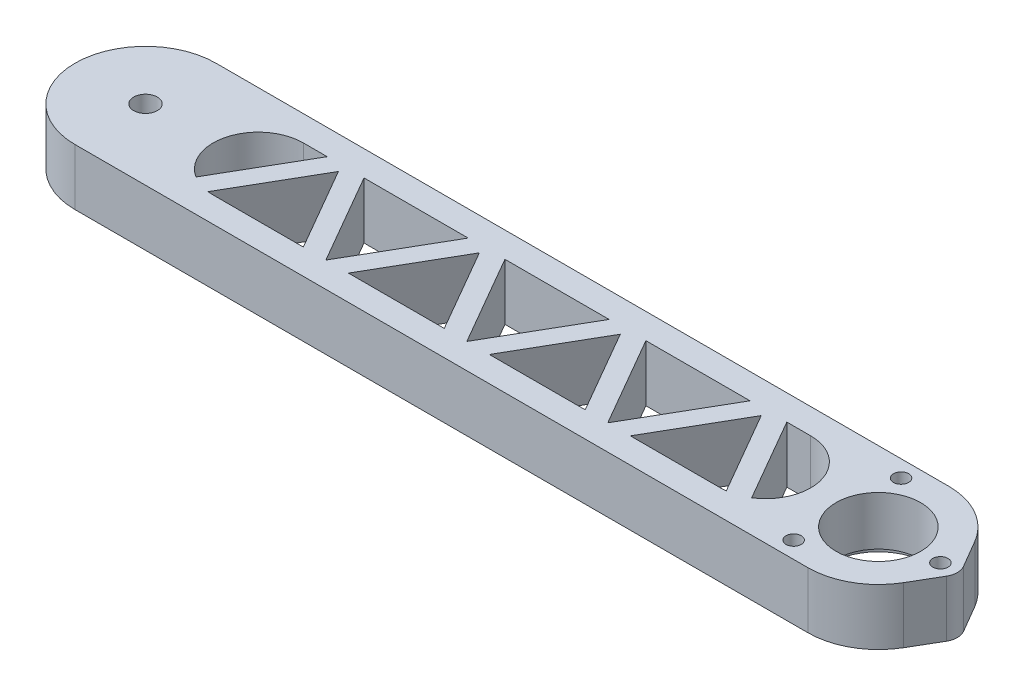
SolidWorks part; units mm, degrees
ref_plane "前视基准面" through (0, 0, 0) normal (0, 0, 1) x (1, 0, 0)
ref_plane "上视基准面" through (0, 0, 0) normal (0, 1, 0) x (1, 0, 0)
ref_plane "右视基准面" through (0, 0, 0) normal (1, 0, 0) x (0, 0, -1)
sketch "草图1" plane through (0, 0, 0) normal (0, 1, 0) x (1, 0, 0)
  line L0 (-65, 0) -> (65, 0) construction
  line L1 (-65, 12.5) -> (65, 12.5)
  line L2 (-65, -12.5) -> (65, -12.5)
  arc A0 (-65, 12.5) -> (-65, -12.5) centre (-65, 0) ccw
  arc A1 (65, -12.5) -> (65, 12.5) centre (65, 0) ccw
  point P2 (0, 0)
  dimension "D2" = 12.5
  dimension "D1" = 130
extrude "凸台-拉伸1" add sketch "草图1" along normal blind 10
sketch "草图10" plane through (0, 0, 0) normal (0, -1, 0) x (1, 0, 0)
  line L0 (75.7955, -6.3014) -> (78.5909, -1.5123)
  line L3 (75.7955, 6.3014) -> (78.5909, 1.5123)
  line L4 (75.7955, -6.3014) -> (75.7955, 6.3014)
  line L5 (76, 0) -> (77.5, 0) construction
  circle A5 centre (76, 0) radius 3 construction
  arc A6 (65, -12.5) -> (65, 12.5) centre (65, 0) ccw construction
  arc A7 (78.5909, -1.5123) -> (78.5909, 1.5123) centre (76, 0) ccw
  dimension "D1" = 6
  dimension "D2" = 1.5
extrude "凸台-拉伸5" add sketch "草图10" against normal up to surface (10 mm away) up to face at (0, 10, 0)
sketch "草图7" plane through (0, 10, 0) normal (0, 1, 0) x (1, 0, 0)
  circle A0 centre (65, 0) radius 7.5
  dimension "D1" = 15
extrude "切除-拉伸2" cut sketch "草图7" against normal up to next
sketch "草图8" plane through (0, 0, 0) normal (0, 1, 0) x (1, 0, 0)
  circle A0 centre (65, 0) radius 8.75
  dimension "D1" = 17.5
extrude "切除-拉伸3" cut sketch "草图8" along normal blind 1.3
sketch "草图9" plane through (0, 0, 0) normal (0, -1, 0) x (1, 0, 0)
  line L0 (65, 0) -> (54, 0) construction
  line L1 (65, 0) -> (59.5, 9.5263) construction
  circle A0 centre (65, 0) radius 11 construction
  circle A5 centre (59.5, 9.5263) radius 1.35
  circle A9 centre (76, 0) radius 1.35
  circle A10 centre (59.5, -9.5263) radius 1.35
  point P12 (65, 0)
  point P15 (65, 0)
  dimension "22" = 22
  dimension "D3" = 2.7
  dimension "D2" = 60
  dimension "D1" = 3
extrude "切除-拉伸4" cut sketch "草图9" against normal up to next
sketch "草图12" plane through (0, 10, 0) normal (0, 1, 0) x (1, 0, 0)
  circle A0 centre (-65, 0) radius 2.1
  dimension "D1" = 4.2
extrude "切除-拉伸5" cut sketch "草图12" against normal up to next
sketch "草图13" plane through (0, 10, 0) normal (0, 1, 0) x (1, 0, 0)
  line L0 (-45, 0) -> (45, 0) construction
  line L1 (-45, 8) -> (45, 8)
  line L2 (-45, -8) -> (45, -8)
  arc A0 (-45, 8) -> (-45, -8) centre (-45, 0) ccw
  arc A1 (45, -8) -> (45, 8) centre (45, 0) ccw
  point P2 (0, 0)
  dimension "D1" = 8
  dimension "D2" = 90
extrude "切除-拉伸6" cut sketch "草图13" against normal up to next
sketch "草图14" plane through (0, 10, 0) normal (0, 1, 0) x (1, 0, 0)
  line L5 (-45, -8) -> (45, -8) construction
  line L6 (45, 8) -> (-45, 8) construction
  line L7 (0, -8) -> (9.2376, 8)
  line L8 (9.2376, 8) -> (13.2376, 8)
  line L9 (13.2376, 8) -> (4, -8)
  line L10 (4, -8) -> (0, -8)
  dimension "D1" = 4
  dimension "D2" = 60
extrude "凸台-拉伸6" add sketch "草图14" against normal up to surface (10 mm away) up to face at (0, 0, 0)
pattern_linear "阵列(线性)1" count 3 spacing 25 along (-1, 0, 0) count 2 spacing 25 along (1, 0, 0) of "凸台-拉伸6" pattern seed only yes
mirror "镜向1" about plane through (0, 0, 0) normal (1, 0, 0) of "阵列(线性)1"
